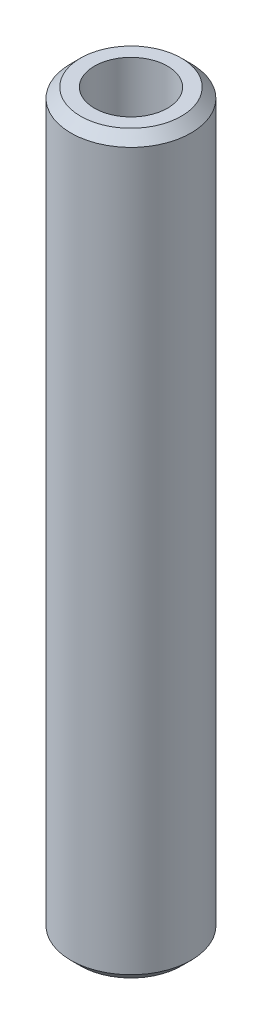
SolidWorks part; units mm, degrees
ref_plane "Front Plane" through (0, 0, 0) normal (0, 0, 1) x (1, 0, 0)
ref_plane "Top Plane" through (0, 0, 0) normal (0, 1, 0) x (1, 0, 0)
ref_plane "Right Plane" through (0, 0, 0) normal (1, 0, 0) x (0, 0, -1)
sketch "Sketch1" plane through (0, 0, 0) normal (0, 1, 0) x (1, 0, 0)
  circle A0 centre (0, 0) radius 35
  dimension "SHAFT_OD" = 70
extrude "Boss-Extrude1" add sketch "Sketch1" along normal blind 428.6145
sketch "Sketch2" plane through (0, 0, 0) normal (0, 1, 0) x (1, 0, 0)
  circle A0 centre (0, 0) radius 21.2779
  dimension "BORE_D" = 42.5558
extrude "Cut-Extrude1" cut sketch "Sketch2" along normal through all
chamfer "Chamfer1" distance 5.6515 angle 45 2 edges at (0, 428.6145, 35) (0, 0, 35)
